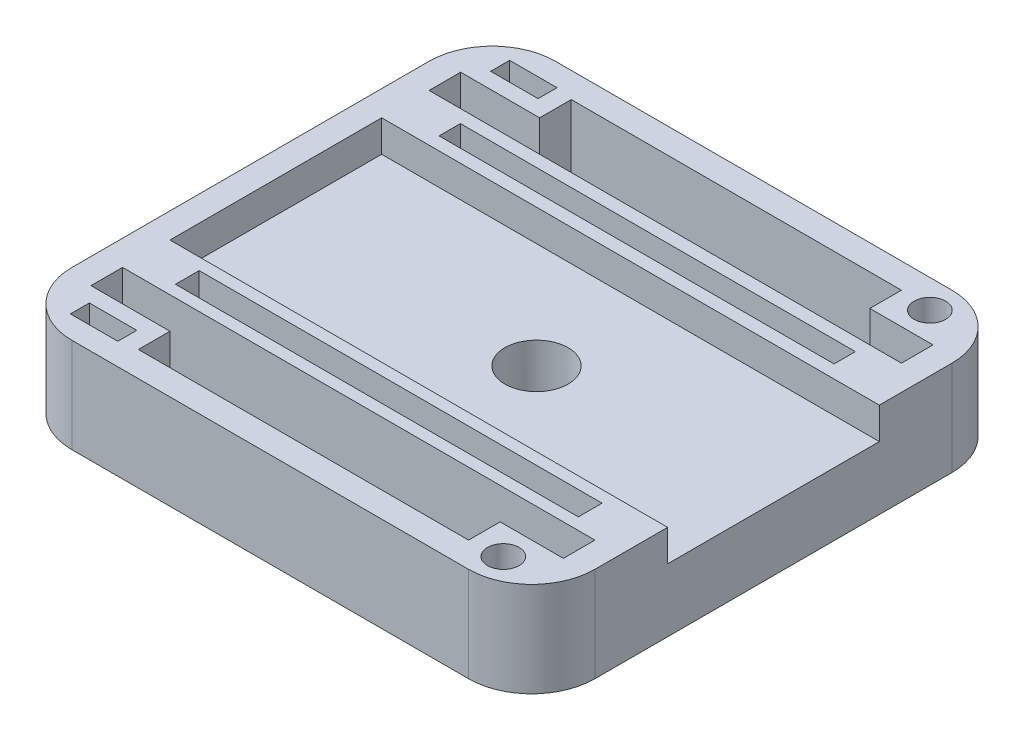
SolidWorks part; units mm, degrees
ref_plane "Front Plane" through (0, 0, 0) normal (0, 0, 1) x (1, 0, 0)
ref_plane "Top Plane" through (0, 0, 0) normal (0, 1, 0) x (1, 0, 0)
ref_plane "Right Plane" through (0, 0, 0) normal (1, 0, 0) x (0, 0, -1)
sketch "Sketch1" plane through (0, 0, 0) normal (0, 1, 0) x (1, 0, 0)
  line L1 (-42.037, -38.862) -> (42.037, -38.862)
  line L2 (-42.037, -38.862) -> (-42.037, 38.862)
  line L3 (-42.037, 38.862) -> (42.037, 38.862)
  line L4 (42.037, -38.862) -> (42.037, 38.862)
  line L5 (-42.037, -38.862) -> (42.037, 38.862) construction
  line L6 (-42.037, 38.862) -> (42.037, -38.862) construction
  point P0 (0, 0)
extrude "Boss-Extrude1" add sketch "Sketch1" along normal blind 5.08 and the other way blind 5.08
sketch "Sketch2" plane through (0, 5.08, 0) normal (0, 1, 0) x (1, 0, 0)
  line L0 (42.037, -38.862) -> (42.037, 38.862) construction
  line L1 (-42.037, 38.862) -> (42.037, 38.862)
  line L2 (-42.037, 38.862) -> (-42.037, 34.798)
  line L3 (-42.037, 34.798) -> (42.037, 34.798)
  line L4 (42.037, 38.862) -> (42.037, 34.798)
  line L6 (-42.037, -38.862) -> (42.037, -38.862)
  line L7 (-42.037, -38.862) -> (-42.037, -34.798)
  line L8 (-42.037, -34.798) -> (42.037, -34.798)
  line L9 (42.037, -38.862) -> (42.037, -34.798)
  line L10 (-42.037, 34.798) -> (-37.973, 34.798)
  line L11 (-42.037, 34.798) -> (-42.037, -34.798)
  line L12 (-42.037, -34.798) -> (-37.973, -34.798)
  line L13 (-37.973, 34.798) -> (-37.973, -34.798)
  line L14 (42.037, 34.798) -> (37.973, 34.798)
  line L15 (42.037, 34.798) -> (42.037, -34.798)
  line L16 (42.037, -34.798) -> (37.973, -34.798)
  line L17 (37.973, 34.798) -> (37.973, -34.798)
  line L18 (-37.973, 34.798) -> (-25.273, 34.798)
  line L19 (-37.973, 34.798) -> (-37.973, 29.718)
  line L20 (-37.973, 29.718) -> (-25.273, 29.718)
  line L21 (-25.273, 34.798) -> (-25.273, 29.718)
  line L22 (37.973, 34.798) -> (27.813, 34.798)
  line L23 (37.973, 34.798) -> (37.973, 29.718)
  line L24 (37.973, 29.718) -> (27.813, 29.718)
  line L25 (27.813, 34.798) -> (27.813, 29.718)
  line L26 (-37.973, -34.798) -> (-25.273, -34.798)
  line L27 (-37.973, -34.798) -> (-37.973, -29.718)
  line L28 (-37.973, -29.718) -> (-25.273, -29.718)
  line L29 (-25.273, -34.798) -> (-25.273, -29.718)
  line L30 (37.973, -34.798) -> (27.813, -34.798)
  line L31 (37.973, -34.798) -> (37.973, -29.718)
  line L32 (37.973, -29.718) -> (27.813, -29.718)
  line L33 (27.813, -34.798) -> (27.813, -29.718)
  dimension "D2" = 4.064
  dimension "D3" = 12.7
  dimension "D4" = 5.08
  dimension "D5" = 10.16
  dimension "D6" = 5.08
  dimension "D7" = 5.08
  dimension "D8" = 12.7
  dimension "D9" = 10.16
  dimension "D10" = 5.08
  dimension "D11" = 4.064
  dimension "D12" = 4.064
  dimension "D13" = 4.064
extrude "Boss-Extrude2" add sketch "Sketch2" along normal blind 5.08 and the other way blind 10.16 contours L21 L3 L15 L17 | L21 L3 L13 L20 | L13 L3 L21 L8 | L8 L29 L28 L13 | L8 L21 L20 L15 | L33 L8 L17 L32 | L3 L17 L8 L15 | L3 L25 L24 L17 region at (0, 5.08, -36.83) region at (-40.005, 5.08, 0) region at (40.005, 5.08, 0) region at (-31.623, 5.08, -32.258) region at (0, 5.08, 36.83) region at (32.893, 5.08, -32.258) region at (-31.623, 5.08, 32.258) region at (32.893, 5.08, 32.258)
sketch "Sketch3" plane through (0, 5.08, 0) normal (0, 1, 0) x (1, 0, 0)
  line L0 (27.813, 34.798) -> (27.813, 29.718) construction
  line L1 (-25.273, 34.798) -> (27.813, 34.798)
  line L2 (-25.273, 34.798) -> (-25.273, 29.718)
  line L3 (-25.273, 29.718) -> (27.813, 29.718)
  line L4 (27.813, 34.798) -> (27.813, 29.718)
  line L6 (27.813, -34.798) -> (27.813, -29.718) construction
  line L7 (-25.273, -34.798) -> (27.813, -34.798)
  line L8 (-25.273, -34.798) -> (-25.273, -29.718)
  line L9 (-25.273, -29.718) -> (27.813, -29.718)
  line L10 (27.813, -34.798) -> (27.813, -29.718)
  dimension "D1" = 5.08
  dimension "D2" = 5.08
extrude "Cut-Extrude1" cut sketch "Sketch3" against normal through all both and the other way through all
sketch "Sketch4" plane through (0, 5.08, 0) normal (0, 1, 0) x (1, 0, 0)
  line L0 (37.973, 29.718) -> (37.973, -29.718) construction
  line L1 (-37.973, 29.718) -> (37.973, 29.718)
  line L2 (-37.973, 29.718) -> (-37.973, 24.638)
  line L3 (-37.973, 24.638) -> (37.973, 24.638)
  line L4 (37.973, 29.718) -> (37.973, 24.638)
  line L6 (-37.973, -29.718) -> (37.973, -29.718)
  line L7 (-37.973, -29.718) -> (-37.973, -24.638)
  line L8 (-37.973, -24.638) -> (37.973, -24.638)
  line L9 (37.973, -29.718) -> (37.973, -24.638)
  dimension "D1" = 5.08
  dimension "D2" = 5.08
extrude "Cut-Extrude2" cut sketch "Sketch4" against normal through all both and the other way through all
sketch "Sketch5" plane through (0, 5.08, 0) normal (0, 1, 0) x (1, 0, 0)
  line L0 (37.973, 29.718) -> (37.973, -29.718) construction
  line L1 (-37.973, 24.638) -> (37.973, 24.638)
  line L2 (-37.973, 24.638) -> (-37.973, 17.018)
  line L3 (-37.973, 17.018) -> (37.973, 17.018)
  line L4 (37.973, 24.638) -> (37.973, 17.018)
  line L5 (37.973, 24.638) -> (37.973, -24.638) construction
  line L6 (-37.973, -24.638) -> (37.973, -24.638)
  line L7 (-37.973, -24.638) -> (-37.973, -17.018)
  line L8 (-37.973, -17.018) -> (37.973, -17.018)
  line L9 (37.973, -24.638) -> (37.973, -17.018)
  line L10 (-42.037, -38.862) -> (42.037, -38.862) construction
  line L11 (42.037, 38.862) -> (-42.037, 38.862) construction
  dimension "D1" = 14.224
  dimension "D2" = 21.844
  dimension "D3" = 14.224
  dimension "D4" = 21.844
extrude "Boss-Extrude3" add sketch "Sketch5" along normal blind 5.08 and the other way blind 10.16
sketch "Sketch10" plane through (0, 5.08, 0) normal (0, 1, 0) x (1, 0, 0)
  line L0 (42.037, 17.018) -> (42.037, -17.018) construction
  circle A0 centre (3.937, 0) radius 5.08
  dimension "D1" = 38.1
extrude "Cut-Extrude4" cut sketch "Sketch10" against normal through all both and the other way through all
sketch "Sketch7" plane through (37.973, 0, 0) normal (-1, 0, 0) x (0, 0, 1)
  line L1 (17.018, 10.16) -> (-17.018, 10.16)
  line L2 (17.018, 10.16) -> (17.018, 5.08)
  line L3 (17.018, 5.08) -> (-17.018, 5.08)
  line L4 (-17.018, 10.16) -> (-17.018, 5.08)
fillet "Fillet1" radius 10.16 4 edges at (42.037, 2.54, -38.862) (-42.037, 2.54, -38.862) (-42.037, 2.54, 38.862) (42.037, 2.54, 38.862)
sketch "Sketch14" plane through (0, 10.16, 0) normal (0, 1, 0) x (1, 0, 0)
  line L0 (37.973, 24.638) -> (-37.973, 24.638) construction
  line L1 (-31.3695, -22.733) -> (33.4005, -22.733)
  line L2 (-31.3695, -22.733) -> (-31.3695, -18.923)
  line L3 (-31.3695, -18.923) -> (33.4005, -18.923)
  line L4 (33.4005, -22.733) -> (33.4005, -18.923)
  line L5 (-31.3695, -22.733) -> (33.4005, -18.923) construction
  line L6 (-31.3695, -18.923) -> (33.4005, -22.733) construction
  line L7 (-30.8356, 19.1135) -> (32.6644, 19.1135)
  line L8 (-30.8356, 19.1135) -> (-30.8356, 22.5425)
  line L9 (-30.8356, 22.5425) -> (32.6644, 22.5425)
  line L10 (32.6644, 19.1135) -> (32.6644, 22.5425)
  line L11 (-30.8356, 19.1135) -> (32.6644, 22.5425) construction
  line L12 (-30.8356, 22.5425) -> (32.6644, 19.1135) construction
  line L13 (-37.973, -24.638) -> (37.973, -24.638) construction
  point P0 (1.0155, -20.828)
  point P5 (0.9144, 20.828)
  dimension "D1" = 3.81
  dimension "D2" = 3.81
sketch "Sketch15" plane through (0, 10.16, 0) normal (0, 1, 0) x (1, 0, 0)
  line L0 (-42.037, 28.702) -> (-42.037, -28.702) construction
  line L1 (31.877, 38.862) -> (-31.877, 38.862) construction
  line L2 (42.037, -28.702) -> (42.037, 28.702) construction
  line L3 (-35.687, 32.258) -> (-28.067, 32.258)
  line L4 (-35.687, 32.258) -> (-35.687, 35.306)
  line L5 (-35.687, 35.306) -> (-28.067, 35.306)
  line L6 (-28.067, 32.258) -> (-28.067, 35.306)
  line L7 (-35.687, 32.258) -> (-28.067, 35.306) construction
  line L8 (-35.687, 35.306) -> (-28.067, 32.258) construction
  circle A0 centre (32.893, 34.29) radius 2.54
  point P0 (-31.877, 33.782)
  point P5 (-31.877, 33.782)
  dimension "D3" = 9.144
  dimension "D1" = 10.16
  dimension "D2" = 5.08
  dimension "D4" = 4.572
extrude "Cut-Extrude6" cut sketch "Sketch15" against normal through all both and the other way through all
mirror "Mirror1" about plane through (0, 0, 0) normal (0, 0, 1) of "Cut-Extrude6"
extrude "Cut-Extrude7" cut sketch "Sketch7" against normal through all
extrude "Cut-Extrude8" cut sketch "Sketch14" against normal blind 3.81
